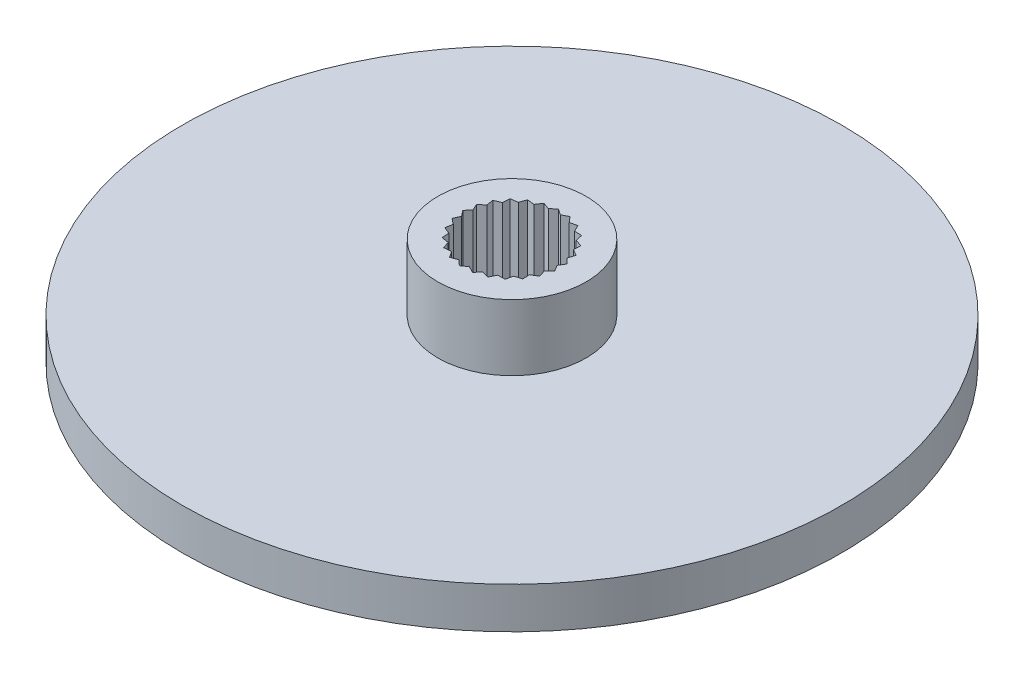
SolidWorks part; units mm, degrees
ref_plane "Front Plane" through (0, 0, 0) normal (0, 0, 1) x (1, 0, 0)
ref_plane "Top Plane" through (0, 0, 0) normal (0, 1, 0) x (1, 0, 0)
ref_plane "Right Plane" through (0, 0, 0) normal (1, 0, 0) x (0, 0, -1)
sketch "Sketch2" plane through (0, 0, 0) normal (0, 1, 0) x (1, 0, 0)
  circle A0 centre (0, 0) radius 20
extrude "Boss-Extrude1" add sketch "Sketch2" along normal blind 2.5
sketch "Sketch3" plane through (0, 2.5, 0) normal (0, 1, 0) x (1, 0, 0)
  circle A0 centre (0, 0) radius 2.75
  circle A1 centre (0, 0) radius 4.5
extrude "Boss-Extrude2" add sketch "Sketch3" along normal blind 4 contours A1 A0 region at (-4.3727, 2.5, 0)
extrude "Cut-Extrude1" cut sketch "Sketch3<3>" against normal through all both and the other way through all contours A0 region at (0, 2.5, 0)
sketch "Sketch3<3>" plane through (0, 2.5, 0) normal (0, 1, 0) x (1, 0, 0) same geometry as "Sketch3"
sketch "Sketch5" plane through (0, 6.5, 0) normal (0, 1, 0) x (1, 0, 0)
  line L0 (0, 0) -> (-0.6227, -3.1858) construction
  line L1 (0, 0) -> (0.1966, -3.3698) construction
  line L2 (0, 0) -> (-0.2333, -3.4568) construction
  line L3 (-0.5276, -2.6989) -> (-0.202, -2.9932)
  line L4 (-0.202, -2.9932) -> (0.1602, -2.7453)
  circle A0 centre (0, 0) radius 3 construction
  circle A1 centre (0, 0) radius 2.75
  circle M6 centre (0, 0) radius 2.75
  dimension "D1" = 7.2
  dimension "D2" = 14.4
extrude "Cut-Extrude2" cut sketch "Sketch5" against normal through all both and the other way through all contours L3 L4 M6 region at (-0.1904, 6.5, 2.8222)
sketch "Sketch6" plane through (0, 0, 0) normal (0, 0, 1) x (1, 0, 0)
  line L0 (0, -0.5187) -> (0, 7.8061) construction
pattern_circular "CirPattern1" count 25 over 360 about axis through (0, -0.5187, 0) along (0, 1, 0) of "Cut-Extrude2" reverse direction yes
